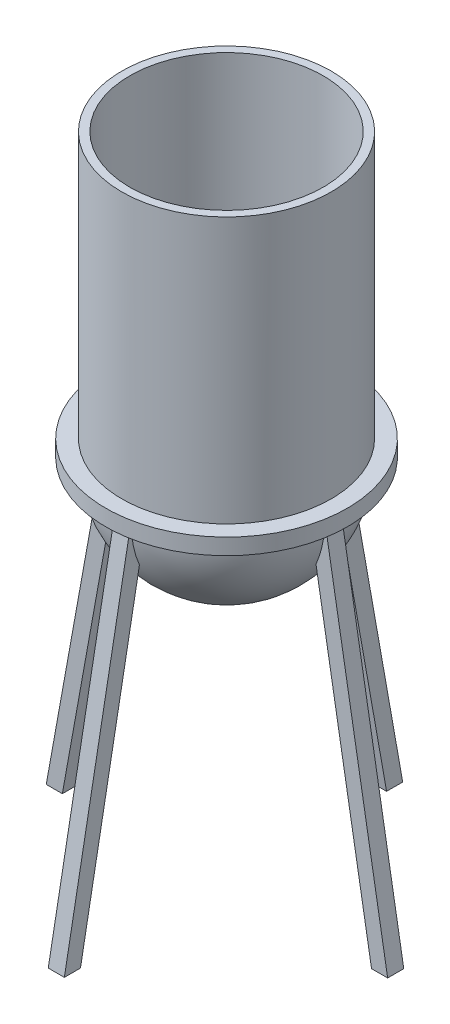
SolidWorks part; units mm, degrees
ref_plane "Front Plane" through (0, 0, 0) normal (0, 0, 1) x (1, 0, 0)
ref_plane "Top Plane" through (0, 0, 0) normal (0, 1, 0) x (1, 0, 0)
ref_plane "Right Plane" through (0, 0, 0) normal (1, 0, 0) x (0, 0, -1)
sketch "Sketch1" plane through (0, 0, 0) normal (0, 1, 0) x (1, 0, 0)
  circle A0 centre (0, 0) radius 330.2
  dimension "D1" = 660.4
extrude "Boss-Extrude1" add sketch "Sketch1" along normal blind 889
sketch "Sketch2" plane through (0, 889, 0) normal (0, 1, 0) x (1, 0, 0)
  circle A1 centre (0, 0) radius 304.8
  dimension "D1" = 609.6
extrude "Cut-Extrude1" cut sketch "Sketch2" against normal blind 876.3
sketch "Sketch5" plane through (0, 0, 0) normal (0, -1, 0) x (1, 0, 0)
  circle A0 centre (0, 0) radius 381
  dimension "D1" = 762
extrude "Boss-Extrude2" add sketch "Sketch5" against normal blind 50.8
sketch "Sketch8" plane through (0, 0, 0) normal (0, -1, 0) x (1, 0, 0)
  line L0 (330.2, 0) -> (-330.2, 0)
  arc A0 (330.2, 0) -> (-330.2, 0) centre (0, 0) ccw
revolve "Revolve1" add sketch "Sketch8" angle 360 about L0
sketch "Sketch11" plane through (0, 0, 0) normal (0, 1, 0) x (1, 0, 0)
  line L0 (304.8, 0) -> (-304.8, 0)
  arc A0 (304.8, 0) -> (-304.8, 0) centre (0, 0) ccw
revolve "Cut-Revolve1" cut sketch "Sketch11" angle 360 mid plane about L0 other way angle 360
sketch "Sketch12" plane through (0, 0, 0) normal (0, 1, 0) x (1, 0, 0)
  circle A0 centre (0, 0) radius 304.8
extrude "Cut-Extrude2" cut sketch "Sketch12" along normal blind 635
sketch "Sketch14" plane through (0, 0, 0) normal (0, 1, 0) x (1, 0, 0)
  line L1 (-22.2603, -330.2) -> (28.5397, -330.2)
  line L2 (-22.2603, -330.2) -> (-22.2603, -279.4)
  line L3 (-22.2603, -279.4) -> (28.5397, -279.4)
  line L4 (28.5397, -330.2) -> (28.5397, -279.4)
  line L5 (-22.2603, -330.2) -> (28.5397, -279.4) construction
  line L6 (-22.2603, -279.4) -> (28.5397, -330.2) construction
  line L11 (279.4, -19.9933) -> (330.2, -19.9933)
  line L12 (279.4, -19.9933) -> (279.4, 30.8067)
  line L13 (-28.5397, 279.4) -> (22.2603, 279.4)
  line L14 (-28.5397, 279.4) -> (-28.5397, 330.2)
  line L15 (-28.5397, 330.2) -> (22.2603, 330.2)
  line L16 (22.2603, 279.4) -> (22.2603, 330.2)
  line L17 (-28.5397, 279.4) -> (22.2603, 330.2) construction
  line L18 (-28.5397, 330.2) -> (22.2603, 279.4) construction
  line L19 (-330.2, -30.7587) -> (-279.4, -30.7587)
  line L20 (-330.2, -30.7587) -> (-330.2, 20.0413)
  line L21 (-330.2, 20.0413) -> (-279.4, 20.0413)
  line L22 (-279.4, -30.7587) -> (-279.4, 20.0413)
  line L23 (-330.2, -30.7587) -> (-279.4, 20.0413) construction
  line L24 (-330.2, 20.0413) -> (-279.4, -30.7587) construction
  line L25 (279.4, 30.8067) -> (330.2, 30.8067)
  line L26 (330.2, -19.9933) -> (330.2, 30.8067)
  line L27 (279.4, -19.9933) -> (330.2, 30.8067) construction
  line L28 (279.4, 30.8067) -> (330.2, -19.9933) construction
  point P1 (3.1397, -304.8)
  point P6 (304.8, 5.4067)
  point P12 (-3.1397, 304.8)
  point P17 (-304.8, -5.3587)
  dimension "D1" = 50.8
  dimension "D3" = 50.8
  dimension "D6" = 50.8
  dimension "D8" = 50.8
  dimension "D2" = 50.8
  dimension "D4" = 50.8
  dimension "D5" = 50.8
  dimension "D7" = 50.8
  dimension "D9" = 304.8
  dimension "D10" = 304.8
  dimension "D11" = 304.8
  dimension "D12" = 304.8
ref_plane "Plane1" through (0, -1143, 0) normal (0, 1, 0) x (1, 0, 0)
ref_axis "Axis1" through (0, 889, 0) along (0, -1, 0)
sketch "Sketch17" plane through (0, -1143, 0) normal (0, 1, 0) x (1, 0, 0)
  line L1 (-482.6, -35.0648) -> (-533.4, -35.0648)
  line L2 (-482.6, -35.0648) -> (-482.6, 15.7352)
  line L3 (-482.6, 15.7352) -> (-533.4, 15.7352)
  line L4 (-533.4, -35.0648) -> (-533.4, 15.7352)
  line L5 (-482.6, -35.0648) -> (-533.4, 15.7352) construction
  line L6 (-482.6, 15.7352) -> (-533.4, -35.0648) construction
  line L7 (-28.7196, -533.4) -> (22.0804, -533.4)
  line L8 (-28.7196, -533.4) -> (-28.7196, -482.6)
  line L9 (-28.7196, -482.6) -> (22.0804, -482.6)
  line L10 (22.0804, -533.4) -> (22.0804, -482.6)
  line L11 (-28.7196, -533.4) -> (22.0804, -482.6) construction
  line L12 (-28.7196, -482.6) -> (22.0804, -533.4) construction
  line L13 (482.6, -25.4) -> (533.4, -25.4)
  line L14 (482.6, -25.4) -> (482.6, 25.4)
  line L15 (482.6, 25.4) -> (533.4, 25.4)
  line L16 (533.4, -25.4) -> (533.4, 25.4)
  line L17 (482.6, -25.4) -> (533.4, 25.4) construction
  line L18 (482.6, 25.4) -> (533.4, -25.4) construction
  line L19 (-28.7196, 482.6) -> (22.0804, 482.6)
  line L20 (-28.7196, 482.6) -> (-28.7196, 533.4)
  line L21 (-28.7196, 533.4) -> (22.0804, 533.4)
  line L22 (22.0804, 482.6) -> (22.0804, 533.4)
  line L23 (-28.7196, 482.6) -> (22.0804, 533.4) construction
  line L24 (-28.7196, 533.4) -> (22.0804, 482.6) construction
  point P0 (-508, -9.6648)
  point P5 (-3.3196, -508)
  point P10 (508, 0)
  point P15 (-3.3196, 508)
  point P20 (0, 0)
  point P23 (-866.064, -367.5607)
  dimension "D1" = 50.8
  dimension "D2" = 50.8
  dimension "D3" = 50.8
  dimension "D4" = 50.8
  dimension "D5" = 50.8
  dimension "D6" = 50.8
  dimension "D7" = 50.8
  dimension "D8" = 50.8
  dimension "D9" = 508
  dimension "D10" = 508
  dimension "D11" = 508
  dimension "D12" = 508
  dimension "D13" = 0
loft "Loft3" add section "Sketch14" section "Sketch17" connector at (28.5397, 0, 279.4) connector at (22.0804, -1143, 482.6)
loft "Loft4" add section "Sketch14<7>" section "Sketch17<4>" connector at (279.4, 0, 19.9933) connector at (482.6, -1143, 25.4)
sketch "Sketch14<7>" plane through (0, 0, 0) normal (0, 1, 0) x (1, 0, 0) same geometry as "Sketch14"
sketch "Sketch17<4>" plane through (0, -1143, 0) normal (0, 1, 0) x (1, 0, 0) same geometry as "Sketch17"
loft "Loft5" add section "Sketch14<8>" section "Sketch17<5>" connector at (22.2603, 0, -279.4) connector at (22.0804, -1143, -482.6)
sketch "Sketch14<8>" plane through (0, 0, 0) normal (0, 1, 0) x (1, 0, 0) same geometry as "Sketch14"
sketch "Sketch17<5>" plane through (0, -1143, 0) normal (0, 1, 0) x (1, 0, 0) same geometry as "Sketch17"
loft "Loft6" add section "Sketch17<6>" section "Sketch14<9>" connector at (-482.6, -1143, 35.0648) connector at (-279.4, 0, 30.7587)
sketch "Sketch17<6>" plane through (0, -1143, 0) normal (0, 1, 0) x (1, 0, 0) same geometry as "Sketch17"
sketch "Sketch14<9>" plane through (0, 0, 0) normal (0, 1, 0) x (1, 0, 0) same geometry as "Sketch14"
